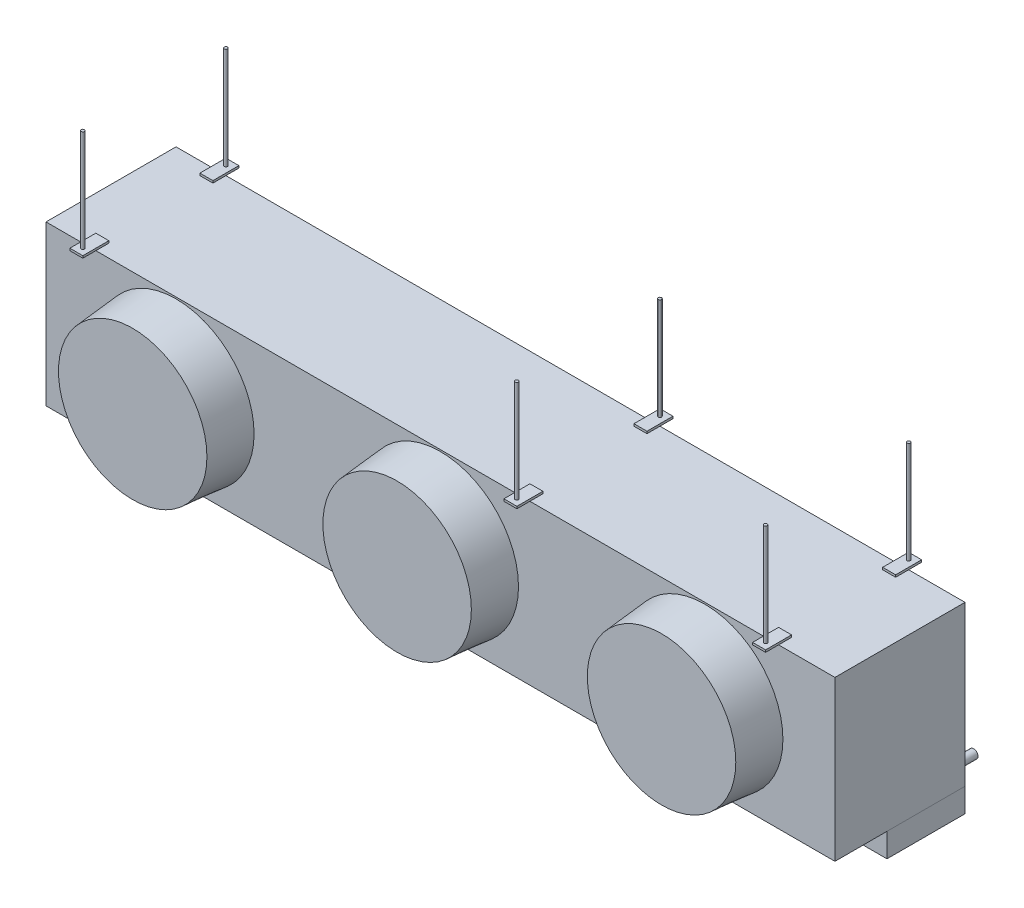
SolidWorks part; units mm, degrees
ref_plane "Front" through (0, 0, 0) normal (0, 0, 1) x (1, 0, 0)
ref_plane "Top" through (0, 0, 0) normal (0, 1, 0) x (1, 0, 0)
ref_plane "Right" through (0, 0, 0) normal (1, 0, 0) x (0, 0, -1)
sketch "Sketch1" plane through (0, 0, 0) normal (0, 1, 0) x (1, 0, 0)
  line L1 (-1155.7, 190.5) -> (1155.7, 190.5)
  line L2 (-1155.7, 190.5) -> (-1155.7, -190.5)
  line L3 (-1155.7, -190.5) -> (1155.7, -190.5)
  line L4 (1155.7, 190.5) -> (1155.7, -190.5)
  line L5 (-1155.7, 190.5) -> (1155.7, -190.5) construction
  line L6 (-1155.7, -190.5) -> (1155.7, 190.5) construction
  point P0 (0, 0)
  dimension "D1" = 2311.4
  dimension "D2" = 381
extrude "Boss-Extrude1" add sketch "Sketch1" along normal blind 466.725
sketch "Sketch2" plane through (0, 0, 190.5) normal (0, 0, 1) x (1, 0, 0)
  line L0 (0, 0) -> (0, 466.725) construction
  line L1 (-1155.7, 466.725) -> (1155.7, 466.725) construction
  line L2 (0, 233.3625) -> (-1155.7, 233.3625) construction
  line L3 (-1155.7, 466.725) -> (-1155.7, 0) construction
  line L4 (0, 233.3625) -> (1155.7, 233.3625) construction
  line L5 (1155.7, 466.725) -> (1155.7, 0) construction
  circle A0 centre (0, 233.3625) radius 228.6
  circle A1 centre (774.7, 233.3625) radius 228.6
  circle A2 centre (-774.7, 233.3625) radius 228.6
  dimension "D1" = 457.2
  dimension "D3" = 381
  dimension "D2" = 381
extrude "Boss-Extrude2" add sketch "Sketch2" along normal blind 127 draft 5
sketch "Sketch3" plane through (0, 466.725, 0) normal (0, 1, 0) x (1, 0, 0)
  line L0 (1155.7, 190.5) -> (-1155.7, 190.5) construction
  line L1 (223.9137, 228.6) -> (262.0137, 228.6)
  line L2 (223.9137, 228.6) -> (223.9137, 152.4)
  line L3 (223.9137, 152.4) -> (262.0137, 152.4)
  line L4 (262.0137, 228.6) -> (262.0137, 152.4)
  line L5 (223.9137, 228.6) -> (262.0137, 152.4) construction
  line L6 (223.9137, 152.4) -> (262.0137, 228.6) construction
  line L8 (223.9137, -152.4) -> (262.0137, -152.4)
  line L9 (223.9137, -152.4) -> (223.9137, -228.6)
  line L10 (223.9137, -228.6) -> (262.0137, -228.6)
  line L11 (262.0137, -152.4) -> (262.0137, -228.6)
  line L12 (223.9137, -152.4) -> (262.0137, -228.6) construction
  line L13 (223.9137, -228.6) -> (262.0137, -152.4) construction
  line L14 (546.1, -190.5) -> (1003.3, -190.5) construction
  line L15 (952.5, 228.6) -> (990.6, 228.6)
  line L16 (952.5, 228.6) -> (952.5, 152.4)
  line L17 (952.5, 152.4) -> (990.6, 152.4)
  line L18 (990.6, 228.6) -> (990.6, 152.4)
  line L19 (952.5, 228.6) -> (990.6, 152.4) construction
  line L20 (952.5, 152.4) -> (990.6, 228.6) construction
  line L21 (952.5, -152.4) -> (990.6, -152.4)
  line L22 (952.5, -152.4) -> (952.5, -228.6)
  line L23 (952.5, -228.6) -> (990.6, -228.6)
  line L24 (990.6, -152.4) -> (990.6, -228.6)
  line L25 (952.5, -152.4) -> (990.6, -228.6) construction
  line L26 (952.5, -228.6) -> (990.6, -152.4) construction
  line L27 (-1003.3, -190.5) -> (-546.1, -190.5) construction
  line L28 (-1047.75, 228.6) -> (-1009.65, 228.6)
  line L29 (-1047.75, 228.6) -> (-1047.75, 152.4)
  line L30 (-1047.75, 152.4) -> (-1009.65, 152.4)
  line L31 (-1009.65, 228.6) -> (-1009.65, 152.4)
  line L32 (-1047.75, 228.6) -> (-1009.65, 152.4) construction
  line L33 (-1047.75, 152.4) -> (-1009.65, 228.6) construction
  line L34 (-1047.75, -152.4) -> (-1009.65, -152.4)
  line L35 (-1047.75, -152.4) -> (-1047.75, -228.6)
  line L36 (-1047.75, -228.6) -> (-1009.65, -228.6)
  line L37 (-1009.65, -152.4) -> (-1009.65, -228.6)
  line L38 (-1047.75, -152.4) -> (-1009.65, -228.6) construction
  line L39 (-1047.75, -228.6) -> (-1009.65, -152.4) construction
  line L40 (-1028.7, -190.5) -> (-1028.7, 190.5) construction
  line L41 (971.55, 190.5) -> (971.55, -190.5) construction
  line L42 (-1028.7, 190.5) -> (0, 190.5) construction
  line L43 (0, 190.5) -> (971.55, 190.5) construction
  line L44 (0, 190.5) -> (971.55, 190.5) construction
  line L45 (-1028.7, 228.6) -> (-1028.7, 209.55) construction
  line L46 (-1028.7, -228.6) -> (-1028.7, -209.55) construction
  line L47 (242.9637, 209.55) -> (242.9637, 190.5) construction
  line L48 (242.9637, -209.55) -> (242.9637, -228.6) construction
  line L49 (971.55, 190.5) -> (971.55, 209.55) construction
  line L50 (971.55, -190.5) -> (971.55, -209.55) construction
  line L51 (-1155.7, 0) -> (-1028.7, 0) construction
  line L53 (-1155.7, 190.5) -> (-1155.7, -190.5) construction
  line L54 (-1155.7, -190.5) -> (1155.7, -190.5) construction
  circle A0 centre (-1028.7, 209.55) radius 4.7625
  circle A1 centre (-1028.7, -209.55) radius 4.7625
  circle A2 centre (971.55, 209.55) radius 4.7625
  circle A3 centre (971.55, -209.55) radius 4.7625
  circle A4 centre (242.9637, -209.55) radius 4.7625
  circle A5 centre (242.9637, 209.55) radius 4.7625
  point P0 (242.9637, 190.5)
  point P7 (242.9637, -190.5)
  point P12 (0, 0)
  point P13 (262.0137, -329.3899)
  point P14 (971.55, 190.5)
  point P19 (971.55, -190.5)
  point P26 (-1028.7, 190.5)
  point P31 (-1028.7, -190.5)
  point P52 (0, 0)
  dimension "D2" = 9.525
  dimension "D5" = 419.1
  dimension "D1" = 127
  dimension "D3" = 19.05
  dimension "D4" = 38.1
  dimension "D6" = 2000.25
  dimension "D7" = 728.5863
extrude "Boss-Extrude3" add sketch "Sketch3" along normal blind 6.35
sketch "Sketch4" plane through (0, 466.725, 0) normal (0, 1, 0) x (1, 0, 0)
  circle A0 centre (-1028.7, 209.55) radius 4.7625 construction
  circle A1 centre (-1028.7, 209.55) radius 4.7625
  circle A2 centre (-1028.7, -209.55) radius 4.7625 construction
  circle A3 centre (-1028.7, -209.55) radius 4.7625
  circle A4 centre (242.9637, -209.55) radius 4.7625 construction
  circle A5 centre (242.9637, -209.55) radius 4.7625
  circle A6 centre (242.9637, 209.55) radius 4.7625 construction
  circle A7 centre (242.9637, 209.55) radius 4.7625
  circle A8 centre (971.55, 209.55) radius 4.7625 construction
  circle A9 centre (971.55, 209.55) radius 4.7625
  circle A10 centre (971.55, -209.55) radius 4.7625 construction
  circle A11 centre (971.55, -209.55) radius 4.7625
extrude "Boss-Extrude4" add sketch "Sketch4" along normal blind 304.8 separate body
sketch "Sketch5" plane through (0, 0, 0) normal (0, -1, 0) x (1, 0, 0)
  line L0 (0, 0) -> (0, -76.2) construction
  line L2 (-1155.7, 38.1) -> (1155.7, 38.1)
  line L3 (-1155.7, 38.1) -> (-1155.7, -190.5)
  line L4 (-1155.7, -190.5) -> (1155.7, -190.5)
  line L5 (1155.7, 38.1) -> (1155.7, -190.5)
  line L6 (-1155.7, 38.1) -> (1155.7, -190.5) construction
  line L7 (-1155.7, -190.5) -> (1155.7, 38.1) construction
  dimension "D1" = 228.6
extrude "Boss-Extrude5" add sketch "Sketch5" along normal blind 69.85 separate body
sketch "Sketch6" plane through (0, -69.85, 0) normal (0, -1, 0) x (1, 0, 0)
  line L0 (0, 38.1) -> (0, -190.5) construction
  line L1 (1155.7, 38.1) -> (-1155.7, 38.1) construction
  line L2 (-1155.7, -190.5) -> (1155.7, -190.5) construction
  circle A0 centre (0, -76.2) radius 12.7
  circle A1 centre (0, -76.2) radius 11.1125
  dimension "D1" = 25.4
  dimension "D2" = 22.225
extrude "Boss-Extrude6" add sketch "Sketch6" along normal blind 44.45
sketch "Sketch7" plane through (0, 0, -190.5) normal (0, 0, -1) x (-1, 0, 0)
  line L0 (0, 0) -> (0, 19.05) construction
  line L1 (0, 19.05) -> (-1104.9, 19.05) construction
  line L2 (0, 19.05) -> (1104.9, 19.05) construction
  line L3 (-1155.7, 466.725) -> (-1155.7, 0) construction
  line L4 (-1155.7, 0) -> (1155.7, 0) construction
  circle A0 centre (-1104.9, 19.05) radius 12.7
  circle A1 centre (1104.9, 19.05) radius 12.7
  dimension "D1" = 25.4
  dimension "D2" = 50.8
  dimension "D3" = 19.05
extrude "Boss-Extrude7" add sketch "Sketch7" along normal blind 76.2
